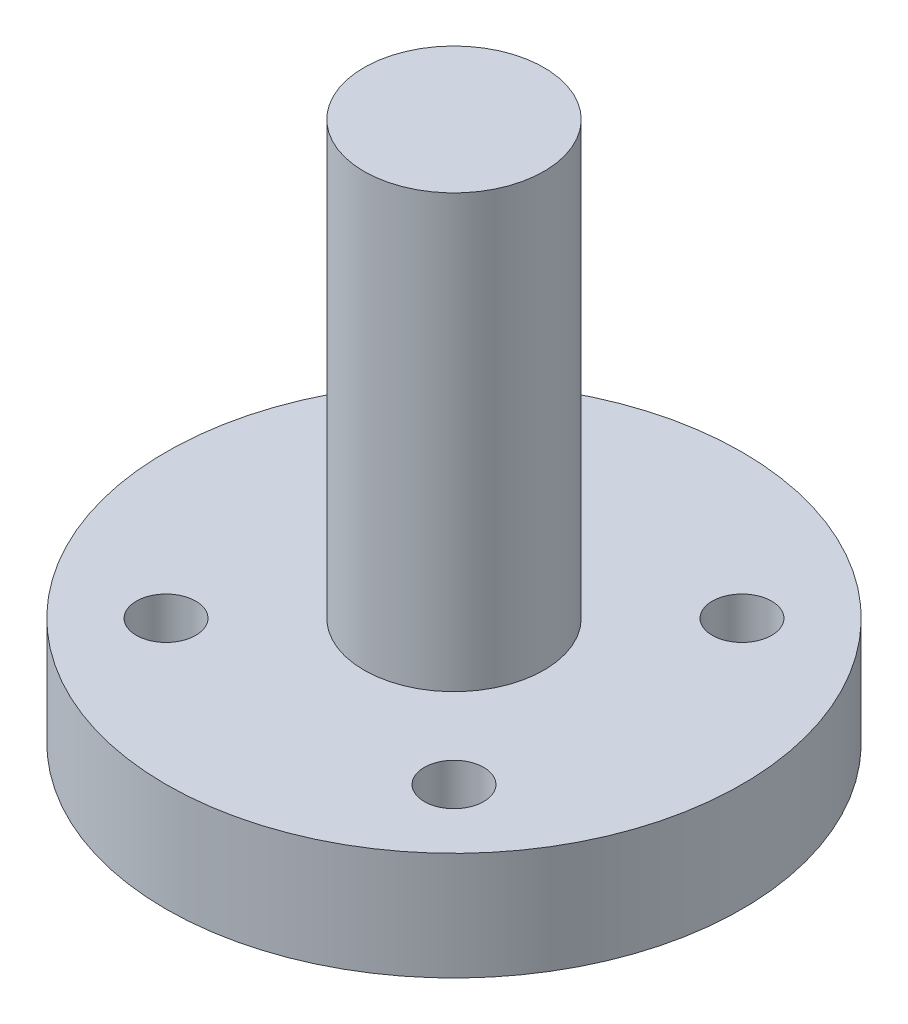
SolidWorks part; units mm, degrees
material "6061 Alloy"
ref_plane "Front Plane" through (0, 0, 0) normal (0, 0, 1) x (1, 0, 0)
ref_plane "Top Plane" through (0, 0, 0) normal (0, 1, 0) x (1, 0, 0)
ref_plane "Right Plane" through (0, 0, 0) normal (1, 0, 0) x (0, 0, -1)
sketch "Sketch1" plane through (0, 0, 0) normal (0, 1, 0) x (1, 0, 0)
  circle A0 centre (0, 0) radius 16
  dimension "D1" = 32
extrude "Boss-Extrude1" add sketch "Sketch1" along normal blind 6
sketch "Sketch3" plane through (0, 6, 0) normal (0, 1, 0) x (1, 0, 0)
  circle A1 centre (0, 0) radius 5
  dimension "D2" = 10
sketch "Sketch4" plane through (0, 0, 0) normal (0, -1, 0) x (1, 0, 0)
  line L1 (8, 8) -> (-8, 8) construction
  line L2 (8, 8) -> (8, -8) construction
  line L3 (8, -8) -> (-8, -8) construction
  line L4 (-8, 8) -> (-8, -8) construction
  line L5 (8, 8) -> (-8, -8) construction
  line L6 (8, -8) -> (-8, 8) construction
  point P0 (0, 0)
  dimension "D1" = 16
  dimension "D2" = 90
hole_wizard "Tap Drill for M4x0.7 Tap1" positions "Sketch5" profile "Sketch6" hole size "M4x0.7" standard "ANSI Metric" end condition through all
sketch "Sketch5" plane through (0, 0, 0) normal (0, -1, 0) x (-1, 0, 0)
  point P0 (-8, 8)
  point P3 (-8, -8)
  point P6 (8, -8)
  point P9 (8, 8)
sketch "Sketch6" plane through (8, 0, -8) normal (1, 0, 0) x (0, 0, -1)
  line L0 (0, 0) -> (0, 6)
  line L1 (0, 6) -> (1.65, 6)
  line L2 (1.65, 6) -> (1.65, 0)
  line L5 (1.65, 0) -> (0, 0)
  line L11 (0, -6.35) -> (0, 107.95) construction
  dimension "Thru Hole Dia." = 3.3
  dimension "Thru Hole Depth" = 6
extrude "Boss-Extrude2" add sketch "Sketch3" along normal blind 24
